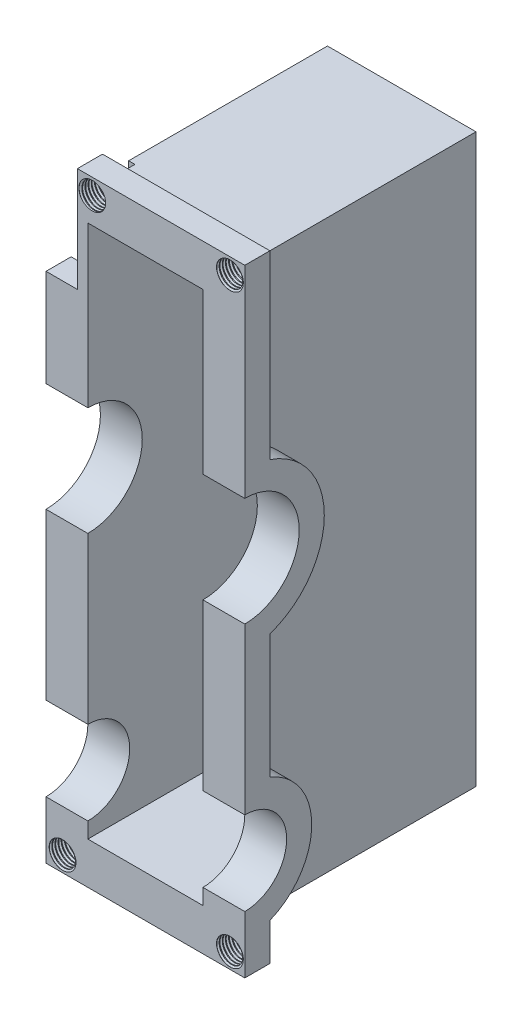
SolidWorks part; units mm, degrees
ref_plane "Спереди" through (0, 0, 0) normal (0, 0, 1) x (1, 0, 0)
ref_plane "Сверху" through (0, 0, 0) normal (0, 1, 0) x (1, 0, 0)
ref_plane "Справа" through (0, 0, 0) normal (1, 0, 0) x (0, 0, -1)
sketch "Эскиз1" plane through (0, 0, 0) normal (0, 0, 1) x (1, 0, 0)
  line L0 (55, -152.5) -> (55, -27.5)
  line L1 (55, -27.5) -> (55, 0)
  line L2 (55, 0) -> (0, 0)
  line L4 (63, 0) -> (63, -263)
  line L5 (0, 0) -> (0, -255)
  line L6 (0, -255) -> (55, -255)
  line L7 (63, -263) -> (-8, -263)
  line L8 (55, -255) -> (55, -152.5)
  line L9 (-8, -263) -> (-8, 8)
  line L10 (-8, 8) -> (63, 8)
  line L11 (63, 8) -> (63, 0)
  line L12 (75, 8) -> (75, -275)
  line L13 (75, -275) -> (-20, -275)
  line L14 (-20, -275) -> (-20, 20)
  line L15 (-20, 20) -> (75, 20)
  line L16 (75, 20) -> (75, 8)
extrude "Бобышка-Вытянуть1" add sketch "Эскиз1" along normal blind 20 contours L11 L10 L9 L7 L4 L8 L6 L5 L2 L1 L0 | L6 L8 L0 L1 L2 L5 region at (27.5, -127.5, 0) region at (60.1985, -131.5, 0)
extrude "Бобышка-Вытянуть2" add sketch "Эскиз1<3>" along normal blind 102.5 from offset 20 contours L11 L4 L7 L9 L10 | L1 L2 L5 L6 L8 L0
sketch "Эскиз1<3>" plane through (0, 0, 0) normal (0, 0, 1) x (1, 0, 0) same geometry as "Эскиз1"
sketch "Эскиз2" plane through (0, 0, 0) normal (1, 0, 0) x (0, 0, -1)
  line L4 (-122.5, 8) -> (-122.5, -263) construction
  line L5 (-122.5, -102.5) -> (-122.5, -227.5)
  circle A0 centre (-122.5, -102.5) radius 26
  circle A1 centre (-122.5, -227.5) radius 20
  point P5 (0, 0)
extrude "Вырез-Вытянуть1" cut sketch "Эскиз2" against normal through all both and the other way through all contours A0 | A1 region at (0, -213.7579, 108.7579) region at (0, -84.6352, 140.3648)
sketch "Эскиз3" plane through (0, 0, 0) normal (1, 0, 0) x (0, 0, -1)
  line L0 (-122.5, -263) -> (-122.5, -247.5)
  line L2 (-122.5, -207.5) -> (-122.5, -128.5)
  line L4 (-122.5, -76.5) -> (-122.5, 8)
  line L5 (-122.5, 8) -> (-110.5, 8)
  line L6 (-122.5, 8) -> (0, 8) construction
  line L7 (-110.5, 8) -> (-110.5, -66.4445)
  line L8 (-122.5, -263) -> (0, -263) construction
  line L9 (-110.5, -263) -> (-122.5, -263)
  line L11 (-110.5, -257.1648) -> (-110.5, -263)
  line L13 (-110.5, -138.5555) -> (-110.5, -197.8352)
  arc A0 (-110.5, -257.1648) -> (-110.5, -197.8352) centre (-122.5, -227.5) ccw
  arc A1 (-122.5, -247.5) -> (-122.5, -207.5) centre (-122.5, -227.5) ccw construction
  arc A2 (-122.5, -247.5) -> (-122.5, -207.5) centre (-122.5, -227.5) ccw
  arc A3 (-122.5, -128.5) -> (-122.5, -76.5) centre (-122.5, -102.5) ccw construction
  arc A4 (-122.5, -128.5) -> (-122.5, -76.5) centre (-122.5, -102.5) ccw
  arc A5 (-110.5, -138.5555) -> (-110.5, -66.4445) centre (-122.5, -102.5) ccw
extrude "Бобышка-Вытянуть3" add sketch "Эскиз3" against normal blind 20
extrude "Бобышка-Вытянуть4" add sketch "Эскиз3<2>" along normal blind 20 from offset 55
sketch "Эскиз3<2>" plane through (0, 0, 0) normal (1, 0, 0) x (0, 0, -1) same geometry as "Эскиз3"
sketch "Эскиз4" plane through (0, 0, 0) normal (0, 1, 0) x (1, 0, 0)
  line L0 (-20, -122.5) -> (75, -122.5)
  line L1 (75, -122.5) -> (75, -110.5)
  line L2 (75, -110.5) -> (-20, -110.5)
  line L3 (-20, -110.5) -> (-20, -122.5)
extrude "Бобышка-Вытянуть5" add sketch "Эскиз4" along normal blind 20
extrude "Бобышка-Вытянуть6" add sketch "Эскиз4<2>" along normal blind 12 from offset 275 offset against normal yes
sketch "Эскиз4<2>" plane through (0, 0, 0) normal (0, 1, 0) x (1, 0, 0) same geometry as "Эскиз4"
sketch "Эскиз5" plane through (0, 0, 0) normal (0, 0, 1) x (1, 0, 0)
  line L0 (-20, 20) -> (-5, 20)
  line L1 (75, 20) -> (-20, 20) construction
  line L2 (-5, 20) -> (-5, -30)
  line L3 (-5, -30) -> (-20, -30)
  line L4 (-20, -66.4445) -> (-20, 20) construction
  line L5 (-20, -30) -> (-20, 20)
extrude "Вырез-Вытянуть2" cut sketch "Эскиз5" against normal blind 30 from offset 125
sketch "Эскиз6" plane through (0, 0, 0) normal (0, 0, 1) x (1, 0, 0)
  circle A0 centre (67.5, 12.5) radius 6
  circle A1 centre (2.5, 12.5) radius 6
  circle A2 centre (67.4989, -267.4989) radius 6
  circle A3 centre (-12.4989, -267.4989) radius 6
  point P5 (-12.4989, -267.9815)
extrude "Вырез-Вытянуть3" cut sketch "Эскиз6" along normal through all from offset 110.5
thread "Резьба1" pitch 1.5 method cut profile "Профиль резьбы1" start angle 0, offset 2, length 14, pitch 1.5, diameter 12
ref_plane "Плоскость1" through (-3.5, 12.5, 124.5) normal (0, -1, 0) x (-1, 0, 0)
sketch "Профиль резьбы1" plane through (-3.5, 12.5, 124.5) normal (0, -1, 0) x (-1, 0, 0)
  line L0 (0, 0) -> (0, 1.5) construction
  line L1 (0, 0) -> (0.8119, 0.4687)
  line L2 (0.8119, 0.4687) -> (0.8119, 0.6562)
  line L3 (0.8119, 0.6562) -> (0, 1.125)
  line L4 (0.8119, 0.5625) -> (0, 0.5625) construction
  line L11 (0, 0) -> (0, 1.125)
  point P2 (0, 0)
  dimension "Pitch" = 1.5
  dimension "Profile_Angle" = 60
  dimension "Profile_Land" = 0.1875
  dimension "Profile_Height" = 0.8119
thread "Резьба2" pitch 1.5 method cut profile "Профиль резьбы2" start angle 0, offset 2, length 14, pitch 1.5, diameter 12
ref_plane "Плоскость2" through (73.5, 12.5, 108.5) normal (0, -1, 0) x (1, 0, 0)
sketch "Профиль резьбы2" plane through (73.5, 12.5, 108.5) normal (0, -1, 0) x (1, 0, 0)
  line L0 (0, 0) -> (0, 1.5) construction
  line L1 (0, 0) -> (0.8119, 0.4687)
  line L2 (0.8119, 0.4687) -> (0.8119, 0.6562)
  line L3 (0.8119, 0.6562) -> (0, 1.125)
  line L4 (0.8119, 0.5625) -> (0, 0.5625) construction
  line L11 (0, 0) -> (0, 1.125)
  point P2 (0, 0)
  dimension "Pitch" = 1.5
  dimension "Profile_Angle" = 60
  dimension "Profile_Land" = 0.1875
  dimension "Profile_Height" = 0.8119
thread "Резьба3" pitch 1.5 method cut profile "Профиль резьбы3" start angle 0, offset 2, length 14, pitch 1.5, diameter 12
ref_plane "Плоскость3" through (73.4989, -267.4989, 108.5) normal (0, -1, 0) x (1, 0, 0)
sketch "Профиль резьбы3" plane through (73.4989, -267.4989, 108.5) normal (0, -1, 0) x (1, 0, 0)
  line L0 (0, 0) -> (0, 1.5) construction
  line L1 (0, 0) -> (0.8119, 0.4687)
  line L2 (0.8119, 0.4687) -> (0.8119, 0.6562)
  line L3 (0.8119, 0.6562) -> (0, 1.125)
  line L4 (0.8119, 0.5625) -> (0, 0.5625) construction
  line L11 (0, 0) -> (0, 1.125)
  point P2 (0, 0)
  dimension "Pitch" = 1.5
  dimension "Profile_Angle" = 60
  dimension "Profile_Land" = 0.1875
  dimension "Profile_Height" = 0.8119
thread "Резьба4" pitch 1.5 method cut profile "Профиль резьбы4" start angle 0, offset 2, length 14, pitch 1.5, diameter 12
ref_plane "Плоскость4" through (-6.4989, -267.4989, 108.5) normal (0, -1, 0) x (1, 0, 0)
sketch "Профиль резьбы4" plane through (-6.4989, -267.4989, 108.5) normal (0, -1, 0) x (1, 0, 0)
  line L0 (0, 0) -> (0, 1.5) construction
  line L1 (0, 0) -> (0.8119, 0.4687)
  line L2 (0.8119, 0.4687) -> (0.8119, 0.6562)
  line L3 (0.8119, 0.6562) -> (0, 1.125)
  line L4 (0.8119, 0.5625) -> (0, 0.5625) construction
  line L11 (0, 0) -> (0, 1.125)
  point P2 (0, 0)
  dimension "Pitch" = 1.5
  dimension "Profile_Angle" = 60
  dimension "Profile_Land" = 0.1875
  dimension "Profile_Height" = 0.8119
